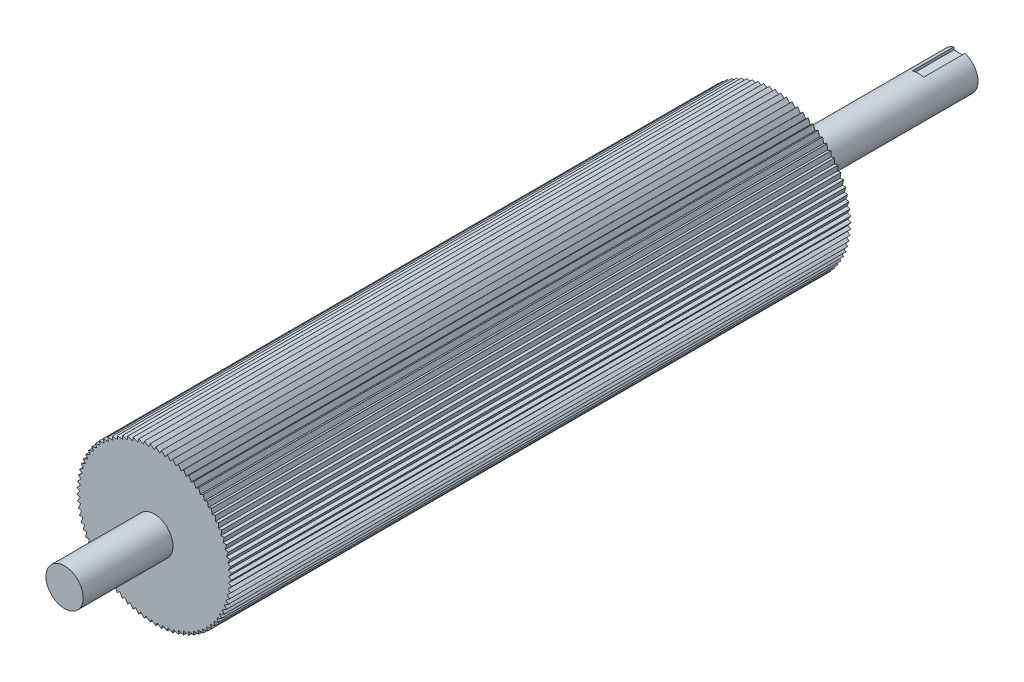
SolidWorks part; units mm, degrees
material "AISI 1020 Steel, Cold Rolled"
ref_plane "Front Plane" through (0, 0, 0) normal (0, 0, 1) x (1, 0, 0)
ref_plane "Top Plane" through (0, 0, 0) normal (0, 1, 0) x (1, 0, 0)
ref_plane "Right Plane" through (0, 0, 0) normal (1, 0, 0) x (0, 0, -1)
sketch "Sketch2" plane through (0, 0, 0) normal (0, 0, 1) x (1, 0, 0)
  circle A0 centre (0, 0) radius 125
  dimension "D1" = 250
extrude "Boss-Extrude1" add sketch "Sketch2" along normal mid plane 1000
sketch "Sketch3" plane through (0, 0, 500) normal (0, 0, 1) x (1, 0, 0)
  circle A0 centre (0, 0) radius 30
  dimension "D1" = 60
extrude "Boss-Extrude2" add sketch "Sketch3" along normal blind 145
sketch "Sketch4" plane through (0, 0, -500) normal (0, 0, -1) x (-1, 0, 0)
  circle A0 centre (0, 0) radius 30
  dimension "D1" = 60
extrude "Boss-Extrude3" add sketch "Sketch4" along normal blind 300
sketch "Sketch11" plane through (0, 0, 500) normal (0, 0, 1) x (1, 0, 0)
  line L0 (0, 14.8002) -> (0, 125) construction
sketch "Sketch15" plane through (0, 0, 500) normal (0, 0, 1) x (1, 0, 0)
  line L0 (0, 120) -> (2.3215, 124.9784)
  line L1 (0, 14.8002) -> (0, 125) construction
  line L2 (0, 120) -> (-6.8709, 124.811)
  circle A1 centre (0, 0) radius 125
  arc A2 (2.3215, 124.9784) -> (-6.8709, 124.811) centre (0, 0) ccw
  dimension "D4" = 120
  dimension "D2" = 25
  dimension "D3" = 55
  dimension "D1" = 0
extrude "Cut-Extrude6" cut sketch "Sketch15" against normal blind 1000
pattern_circular "CirPattern1" count 85 over 360 about axis through (0, 0, 0) along (0, 0, 1) of "Cut-Extrude6"
ref_plane "Plane1" through (0, 0, 50) normal (0, 0, 1) x (1, 0, 0)
sketch "Sketch16" plane through (0, 0, -800) normal (0, 0, -1) x (-1, 0, 0)
  line L1 (-9, 24.5) -> (9, 24.5)
  line L2 (-9, 24.5) -> (-9, 35.5)
  line L3 (-9, 35.5) -> (9, 35.5)
  line L4 (9, 24.5) -> (9, 35.5)
  line L5 (-9, 24.5) -> (9, 35.5) construction
  line L6 (-9, 35.5) -> (9, 24.5) construction
  circle A0 centre (0, 0) radius 30 construction
  circle A1 centre (0, 0) radius 30 construction
  point P0 (0, 30)
  dimension "D1" = 18
  dimension "D2" = 11
extrude "Cut-Extrude7" cut sketch "Sketch16" against normal blind 67
